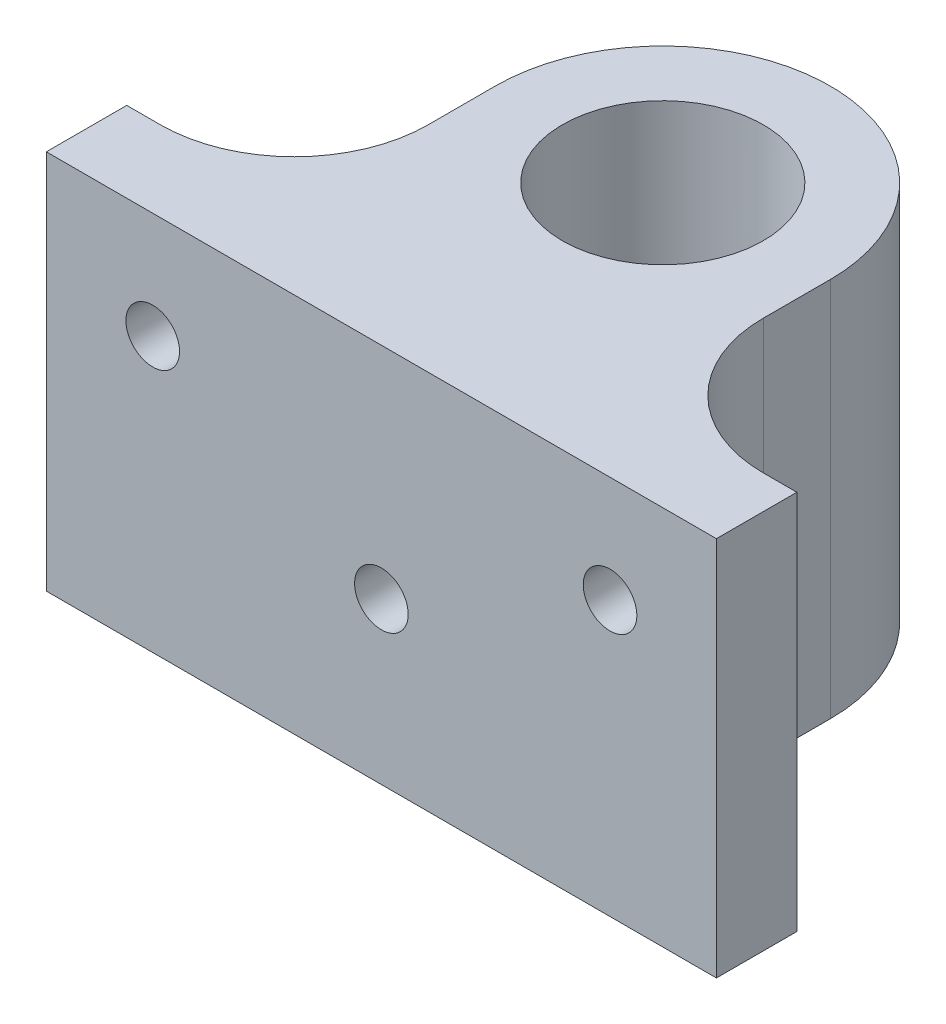
SolidWorks part; units mm, degrees
ref_plane "Front Plane" through (0, 0, 0) normal (0, 0, 1) x (1, 0, 0)
ref_plane "Top Plane" through (0, 0, 0) normal (0, 1, 0) x (1, 0, 0)
ref_plane "Right Plane" through (0, 0, 0) normal (1, 0, 0) x (0, 0, -1)
sketch "Profile-Sketch1" plane through (0, 0, 0) normal (0, 1, 0) x (1, 0, 0)
  line L0 (-25, -21) -> (25, -21)
  line L1 (25, -21) -> (25, -15)
  line L2 (-25, -21) -> (-25, -15)
  line L3 (-25, -15) -> (-22.5, -15)
  line L4 (-12.5, -5) -> (-12.5, 0)
  line L5 (25, -15) -> (22.5, -15)
  line L6 (12.5, -5) -> (12.5, 0)
  circle A0 centre (0, 0) radius 7.5
  arc A6 (12.5, 0) -> (-12.5, 0) centre (0, 0) ccw
  arc A7 (22.5, -15) -> (12.5, -5) centre (22.5, -5) cw
  arc A8 (-12.5, -5) -> (-22.5, -15) centre (-22.5, -5) cw
  dimension "D1" = 15
  dimension "D2" = 12.5
  dimension "D7" = 10
  dimension "D3" = 50
  dimension "D4" = 25
  dimension "D5" = 21
  dimension "D6" = 6
extrude "Profile-Boss-Extrude2" add sketch "Profile-Sketch1" along normal blind 28.3901
sketch "FasteningHoleSketch3" plane through (0, 0, 21) normal (0, 0, 1) x (1, 0, 0)
  line L0 (25, 28.3901) -> (25, 0) construction
  line L1 (-25, 28.3901) -> (-25, 0) construction
  line L2 (-25, 0) -> (25, 0) construction
  circle A2 centre (-17.0625, 20.4526) radius 2
  circle A3 centre (17.0625, 20.4526) radius 2
  dimension "D3" = 4
  dimension "D6" = 7.9375
  dimension "D2" = 20.4526
  dimension "D1" = 7.9375
extrude "FasteningHoleCut-Extrude8" cut sketch "FasteningHoleSketch3" against normal through all
sketch "LM8UUFasteningHoleSketch5" plane through (0, 0, 21) normal (0, 0, 1) x (1, 0, 0)
  line L0 (25, 28.3901) -> (25, 0) construction
  line L1 (-25, 0) -> (25, 0) construction
  line L2 (-25, 28.3901) -> (25, 28.3901) construction
  circle A0 centre (0, 12) radius 2
  circle A1 centre (-17.0625, 20.4526) radius 2 construction
  dimension "D1" = 25
  dimension "D2" = 12
  dimension "D3" = 16.3901
extrude "LM8UUFasteningHoleCut-Extrude9" cut sketch "LM8UUFasteningHoleSketch5" against normal through all
equation "\"RailThickness\"= .125in'Spec"
equation "\"LM8UUDiameter\"= 15mm"
equation "\"MidLeftOrRightSideRailHeight\"= 2.0in"
equation "\"RodStabilizerLength\"= 50mm"
equation "\"HoleOffsetFromEdge\"= \"RailThickness\" * 2.5"
equation "\"StepperMountingHoleOffsetFromItsSide\"= 5.5mm'Spec"
equation "\"StepperMountingHoleOffsetFromLeftOrRightSide\"= \"StepperMountingHoleOffsetFromItsSide\" + \"RailThickness\""
equation "\"StepperMountingHoleDistance\"= 31mm'Spec"
equation "\"LM8UUHeight\"= 24mm'Spec"
equation "\"ZAxisLeadScrewLength\"= 200mm"
equation "\"LegHeight\"= 70mm'Space needed for PSU/Stepper/Electronics"
equation "\"V1 BottomOfLowerRail\"= \"LegHeight\""
equation "\"StepperShaftLength\"= 24mm'Pulley will be attached to the end"
equation "\"V2 ToBedAtTopOfZAxis\"= \"V1 BottomOfLowerRail\" - \"LowerEnclosureThickness\" + \"StepperShaftLength\" + \"ZAxisLeadScrewLength\" - \"LM8UUHeight\" / 2"
equation "\"HotEndToTopOfXAxisGB\"= 63.315144mm'Measured from the100.Should be 63.315144"
equation "\"TopOfGBToBottomOfLinearRail\"= \"LinearGBWidth\" / 2 + \"LinearRailWidth\" / 2"
equation "\"LinearGBWidth\"= 27mm'Spec"
equation "\"V5 ToBottomOfXAxisLinearRail\"= \"V4 ToTopOfBuildPlate/HotEndTip\" + \"HotEndToTopOfXAxisGB\" - \"TopOfGBToBottomOfLinearRail\""
equation "\"LinearRailWidth\"= 12mm'Spec"
equation "\"V6 ToMiddleOfYAxisGantryBlock\"= \"V5 ToBottomOfXAxisLinearRail\" - \"GABHeight\" / 2'Equals 325.31514"
equation "\"GABUpperHeight\"= 6mm"
equation "\"GABMidWallHeight\"= 28mm'Must equal 28 or changes alignment"
equation "\"BedToBuildPlateStandoffLength\"= 15mm"
equation "\"BuildPlateHeight\"= 8mm'Spec"
equation "\"V4 ToTopOfBuildPlate/HotEndTip\"= \"V2 ToBedAtTopOfZAxis\" + \"BedToBuildPlateStandoffLength\" + \"BuildPlateHeight\""
equation "\"RodStabilizerHeight\"= \"V8 ToBottomOfMidSideRail\" - \"V2 ToBedAtTopOfZAxis\" + \"HoleOffsetFromEdge\" * 2"
equation "\"LowerEnclosureThickness\"= 5mm"
equation "\"D1@Profile-Sketch1\" = \"LM8UUDiameter\""
equation "\"D3@Profile-Sketch1\" = \"RodStabilizerLength\""
equation "\"D4@Profile-Sketch1\" = \"RodStabilizerLength\" / 2"
equation "\"RodStabilizerWidthFromMidRailToZAxisRodCenter\"= \"StepperMountingHoleOffsetFromLeftOrRightSide\" + \"StepperMountingHoleDistance\" / 2 - \"RailThickness\""
equation "\"StandardWallThickness\"= 3mm"
equation "\"D6@Profile-Sketch1\" = \"StandardWallThickness\" * 2"
equation "\"D1@Profile-Boss-Extrude2\"= \"RodStabilizerHeight\""
equation "\"D6@FasteningHoleSketch3\"=\"HoleOffsetFromEdge\""
equation "\"D2@LM8UUFasteningHoleSketch5\"=\"LM8UUHeight\"/2"
equation "\"V8 ToTopOfMidSideRail\"= \"V6 ToMiddleOfYAxisGantryBlock\" + \"MidSideRailVerticalOffset\""
equation "\"D5@Profile-Sketch1\"=\"RodStabilizerWidthFromMidRailToZAxisRodCenter\""
equation "\"RodStabilizerMountingHoleYOffsetFromBottom\"= \"RodStabilizerHeight\" - \"HoleOffsetFromEdge\""
equation "\"D2@FasteningHoleSketch3\"=\"RodStabilizerMountingHoleYOffsetFromBottom\""
equation "\"D3@FasteningHoleSketch3\"=\"M3HeatInsertHoleDiameter\""
equation "\"GABLowerHeight\"= 3mm"
equation "\"GABHeight\"= \"GABLowerHeight\" + \"GABMidWallHeight\" + \"GABUpperHeight\""
equation "\"V8 ToBottomOfMidSideRail\"= \"V8 ToTopOfMidSideRail\" - \"MidLeftOrRightSideRailHeight\"'Equals 289.51514"
equation "\"D1@LM8UUFasteningHoleSketch5\"=\"RodStabilizerLength\"/2"
equation "\"MidSideRailVerticalOffset\"= \"LinearRailWidth\" + 3mm'Allows space for RodStabilizer to attach to bottom of MidSideRail"
equation "\"M3HeatInsertHoleDiameter\"= 4mm'Spec"
